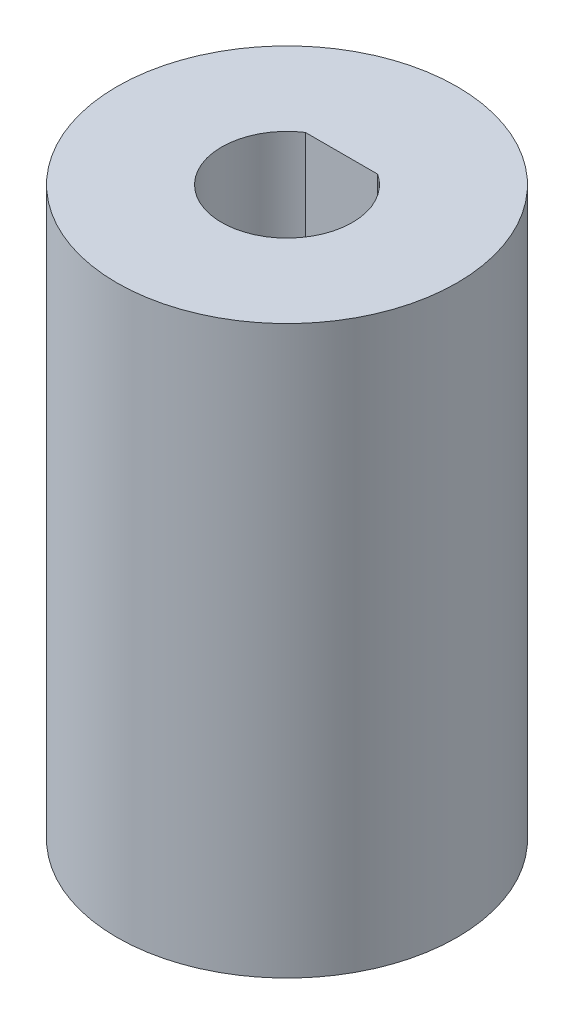
SolidWorks part; units mm, degrees
ref_plane "Front Plane" through (0, 0, 0) normal (0, 0, 1) x (1, 0, 0)
ref_plane "Top Plane" through (0, 0, 0) normal (0, 1, 0) x (1, 0, 0)
ref_plane "Right Plane" through (0, 0, 0) normal (1, 0, 0) x (0, 0, -1)
sketch "Sketch1" plane through (0, 0, 0) normal (0, 1, 0) x (1, 0, 0)
  circle A0 centre (0, 0) radius 7.8
  dimension "D1" = 15.6
extrude "Boss-Extrude1" add sketch "Sketch1" along normal blind 26
sketch "Sketch2" plane through (0, 0, 0) normal (0, 1, 0) x (1, 0, 0)
  line L0 (-1.6583, 2.5) -> (1.6583, 2.5)
  circle A1 centre (0, 0) radius 3
  point P6 (-1.6583, 2.5)
  point P7 (0, -3)
  dimension "D1" = 6
  dimension "D2" = 5.5
extrude "Cut-Extrude3" cut sketch "Sketch2" along normal through all contours L0 A1 region at (0, 0, 0.112)
